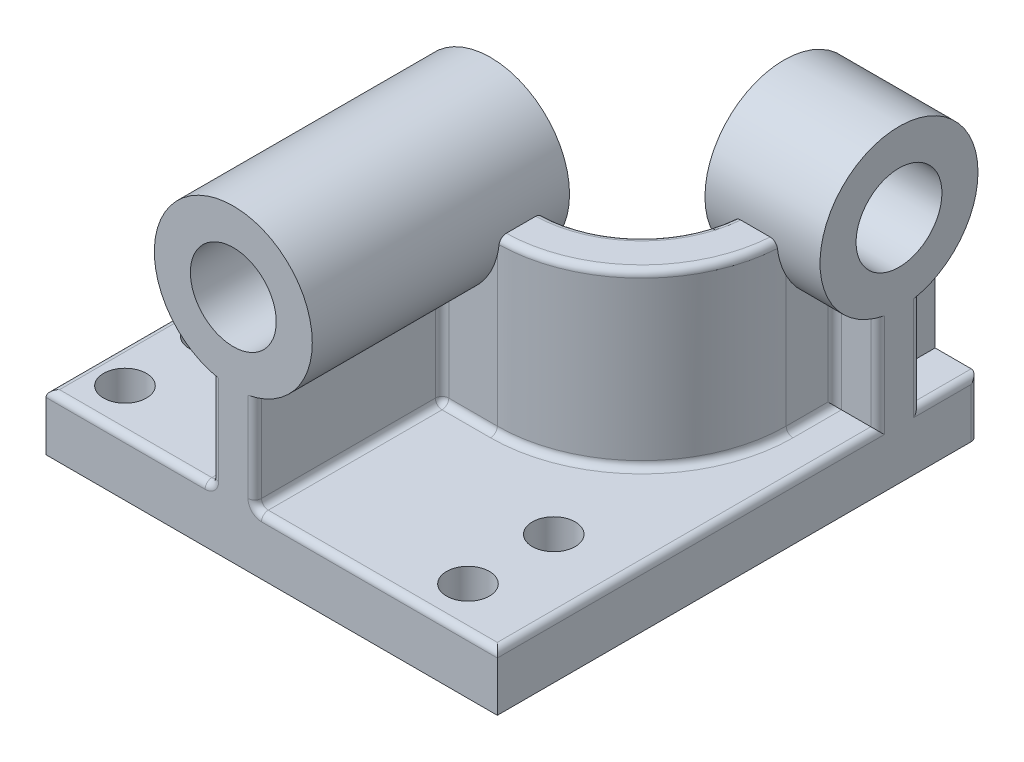
SolidWorks part; units mm, degrees
ref_plane "Front Plane" through (0, 0, 0) normal (0, 0, 1) x (1, 0, 0)
ref_plane "Top Plane" through (0, 0, 0) normal (0, 1, 0) x (1, 0, 0)
ref_plane "Right Plane" through (0, 0, 0) normal (1, 0, 0) x (0, 0, -1)
sketch "Sketch2" plane through (0, 0, 0) normal (0, 1, 0) x (1, 0, 0)
  line L0 (-100, -106.5) -> (-100, -4.5)
  line L1 (100, -106.5) -> (-100, -106.5)
  line L2 (100, -106.5) -> (100, 106.5)
  line L5 (0, 0) -> (0, -106.5) construction
  line L6 (-100, -4.5) -> (62, -4.5)
  line L7 (100, 106.5) -> (62, 106.5)
  line L8 (62, -4.5) -> (62, 106.5)
  line L9 (0, 0) -> (100, 0) construction
  point P0 (0, 0)
  dimension "D4" = 38
  dimension "D1" = 200
  dimension "D2" = 213
  dimension "D3" = 102
extrude "Boss-Extrude2" add sketch "Sketch2" along normal blind 25
fillet "Fillet1" radius 45 1 edges at (62, 12.5, 4.5)
sketch "Sketch7" plane through (0, 0, 106.5) normal (0, 0, 1) x (1, 0, 0)
  line L0 (-100, 25) -> (-100, 0) construction
  line L1 (-17, 102) -> (-17, 25) construction
  line L2 (-100, 25) -> (100, 25) construction
  line L3 (-100, 0) -> (100, 0) construction
  circle A0 centre (-17, 102) radius 19.025
  circle A1 centre (-17, 102) radius 35
  dimension "D1" = 70
  dimension "D2" = 38.05
  dimension "D3" = 83
  dimension "D4" = 102
extrude "Boss-Extrude3" add sketch "Sketch7" against normal blind 114 separate body
sketch "Sketch8" plane through (100, 0, 0) normal (1, 0, 0) x (0, 0, -1)
  line L0 (106.5, 25) -> (106.5, 0) construction
  line L1 (-106.5, 0) -> (106.5, 0) construction
  line L2 (71.5, 102) -> (71.5, 25) construction
  line L3 (-106.5, 25) -> (106.5, 25) construction
  circle A0 centre (71.5, 102) radius 19.025
  circle A1 centre (71.5, 102) radius 35
  dimension "D1" = 38.05
  dimension "D2" = 70
  dimension "D3" = 35
  dimension "D4" = 102
extrude "Boss-Extrude4" add sketch "Sketch8" against normal blind 51 separate body
sketch "Sketch9" plane through (0, 25, 0) normal (0, 1, 0) x (1, 0, 0)
  line L3 (17, -4.5) -> (-100, -4.5) construction
  line L4 (17, -4.5) -> (-52, -4.5)
  line L5 (81, 106.5) -> (81, 40.5)
  line L6 (17, -23.5) -> (-100, -23.5)
  line L7 (81, 106.5) -> (81, 40.5)
  line L8 (17, -23.5) -> (-52, -23.5)
  line L9 (62, 106.5) -> (62, 40.5) construction
  line L10 (62, 106.5) -> (62, 40.5)
  line L11 (-52, -4.5) -> (-52, -23.5)
  line L12 (62, 106.5) -> (81, 106.5)
  line L13 (-52, 7.5) -> (-52, -106.5) construction
  arc A3 (17, -4.5) -> (62, 40.5) centre (17, 40.5) ccw construction
  arc A4 (17, -23.5) -> (81, 40.5) centre (17, 40.5) ccw
  arc A5 (17, -23.5) -> (81, 40.5) centre (17, 40.5) ccw
  arc A6 (17, -4.5) -> (62, 40.5) centre (17, 40.5) ccw
  dimension "D1" = 19
extrude "Boss-Extrude5" add sketch "Sketch9" along normal blind 76
extrude "Cut-Extrude1" cut sketch "Sketch8<2>" against normal through all contours A0 region at (100, 102, -71.5)
sketch "Sketch8<2>" plane through (100, 0, 0) normal (1, 0, 0) x (0, 0, -1) same geometry as "Sketch8"
extrude "Cut-Extrude2" cut sketch "Sketch7<2>" against normal through all contours A0 region at (-17, 102, 106.5)
sketch "Sketch7<2>" plane through (0, 0, 106.5) normal (0, 0, 1) x (1, 0, 0) same geometry as "Sketch7"
sketch "Sketch10" plane through (0, 0, 106.5) normal (0, 0, 1) x (1, 0, 0)
  line L0 (-26.5, 25) -> (-7.5, 25)
  line L1 (-100, 25) -> (100, 25) construction
  line L2 (-7.5, 25) -> (-7.5, 68.3139)
  line L3 (-26.5, 25) -> (-26.5, 68.3139)
  line L4 (-100, 25) -> (-100, 0) construction
  circle A0 centre (-17, 102) radius 35 construction
  arc A1 (-26.5, 68.3139) -> (-7.5, 68.3139) centre (-17, 102) ccw
  point P2 (-17, 25)
  dimension "D1" = 83
  dimension "D2" = 19
extrude "Boss-Extrude6" add sketch "Sketch10" against normal up to next
sketch "Sketch11" plane through (100, 0, 0) normal (1, 0, 0) x (0, 0, -1)
  line L0 (62, 25) -> (81, 25)
  line L1 (-106.5, 25) -> (106.5, 25) construction
  line L2 (81, 25) -> (81, 68.3139)
  line L3 (62, 25) -> (62, 68.3139)
  line L4 (106.5, 25) -> (106.5, 0) construction
  circle A0 centre (71.5, 102) radius 35 construction
  arc A1 (62, 68.3139) -> (81, 68.3139) centre (71.5, 102) ccw
  point P7 (57.7792, 69.8016)
  point P11 (71.5, 25)
  dimension "D1" = 35
  dimension "D2" = 19
extrude "Boss-Extrude7" add sketch "Sketch11" against normal up to next
sketch "Sketch12" plane through (0, 25, 0) normal (0, 1, 0) x (1, 0, 0)
  line L0 (-7.5, -106.5) -> (100, -106.5) construction
  line L1 (100, -106.5) -> (100, 62) construction
  line L2 (68, -87.5) -> (68, -49.5) construction
  line L3 (-84, -87.5) -> (68, -87.5) construction
  line L7 (-84, -49.5) -> (68, -49.5) construction
  circle A0 centre (68, -49.5) radius 9.5
  circle A1 centre (68, -87.5) radius 9.5
  circle A2 centre (-84, -49.5) radius 9.5
  circle A3 centre (-84, -87.5) radius 9.5
  dimension "D1" = 19
  dimension "D2" = 19
  dimension "D3" = 32
  dimension "D4" = 38
  dimension "D5" = 152
  dimension "D6" = 152
extrude "Cut-Extrude3" cut sketch "Sketch12" against normal through all
fillet "Fillet2" radius 3 25 edges at (-52, 63, 4.5) (-7.5, 46.657, 106.5) (4.75, 25, 23.5) (81, 25, -51.25) (47.7398, 101, -7.6356) (-26.5, 25, 65) (-52, 25, 14) (-39.25, 25, 23.5) (-26.5, 46.657, 23.5) (-76, 25, 4.5) (-100, 25, 55.5) (-63.25, 25, 106.5) (-7.5, 46.657, 23.5) (81, 46.657, -81) (81, 46.657, -62) (100, 12.5, -106.5) (100, 25, -93.75) (100, 46.657, -81) (100, 46.657, -62) (61.1809, 101, 5.8038) (-26.5, 46.657, 106.5) (100, 25, 22.25) (46.25, 25, 106.5) (-7.5, 25, 65) (62.2548, 25, 4.7548)
